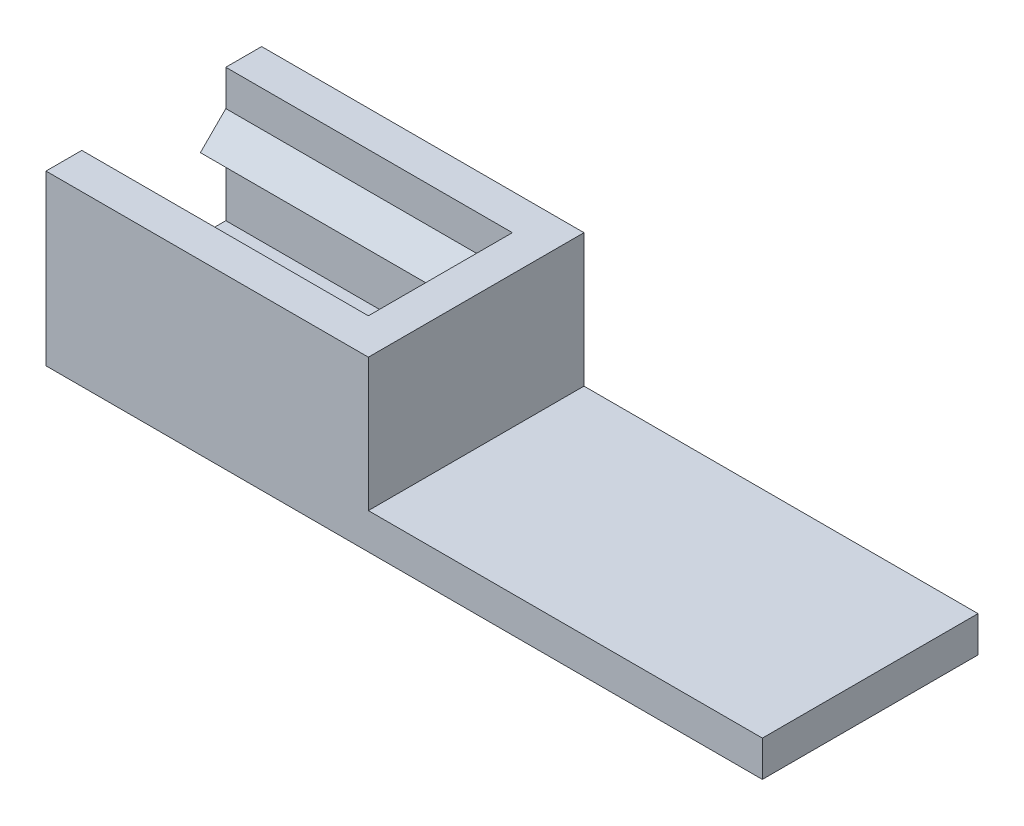
SolidWorks part; units mm, degrees
ref_plane "Front Plane" through (0, 0, 0) normal (0, 0, 1) x (1, 0, 0)
ref_plane "Top Plane" through (0, 0, 0) normal (0, 1, 0) x (1, 0, 0)
ref_plane "Right Plane" through (0, 0, 0) normal (1, 0, 0) x (0, 0, -1)
sketch "Sketch2" plane through (0, 0, 0) normal (1, 0, 0) x (0, 0, -1)
  line L0 (15.05, 0) -> (-15.05, 0)
  line L1 (-15.05, 0) -> (-15.05, 23.55)
  line L2 (-15.05, 23.55) -> (-10.05, 23.55)
  line L3 (-10.05, 23.55) -> (-10.05, 18.55)
  line L4 (-10.05, 18.55) -> (-6.5, 15)
  line L5 (-6.5, 15) -> (-10.05, 11.45)
  line L6 (-10.05, 11.45) -> (-10.05, 5)
  line L7 (-10.05, 5) -> (10.05, 5)
  line L9 (0, 12.925) -> (0, -12.925) construction
  line L10 (10.05, 11.45) -> (10.05, 5)
  line L11 (6.5, 15) -> (10.05, 11.45)
  line L12 (10.05, 18.55) -> (6.5, 15)
  line L13 (10.05, 23.55) -> (10.05, 18.55)
  line L14 (15.05, 23.55) -> (10.05, 23.55)
  line L15 (15.05, 0) -> (15.05, 23.55)
  point P19 (0, 5)
  point P25 (0, 0)
  dimension "D1" = 15.05
  dimension "D2" = 5
  dimension "D3" = 45
  dimension "D4" = 6.45
  dimension "D5" = 3.55
  dimension "D6" = 5
  dimension "D7" = 5
extrude "Boss-Extrude1" add sketch "Sketch2" along normal mid plane 40
sketch "Sketch3" plane through (20, 0, 0) normal (1, 0, 0) x (0, 0, -1)
  line L0 (-15.05, 23.55) -> (-15.05, 0) construction
  line L2 (-15.05, 5) -> (15.05, 5)
  line L3 (-15.05, 5) -> (-15.05, 0)
  line L4 (-15.05, 0) -> (15.05, 0)
  line L5 (15.05, 5) -> (15.05, 0)
  dimension "D1" = 5
extrude "Boss-Extrude2" add sketch "Sketch3" along normal blind 60
sketch "Sketch4" plane through (0, 5, 0) normal (0, 1, 0) x (1, 0, 0)
  line L0 (80, -15.05) -> (20, -15.05) construction
  line L1 (20, 15.05) -> (25, 15.05)
  line L2 (20, 15.05) -> (20, -15.05)
  line L3 (20, -15.05) -> (25, -15.05)
  line L4 (25, 15.05) -> (25, -15.05)
  dimension "D1" = 5
extrude "Boss-Extrude3" add sketch "Sketch4" along normal up to surface (18.55 mm away) up to face at (0, 23.55, -12.55)
